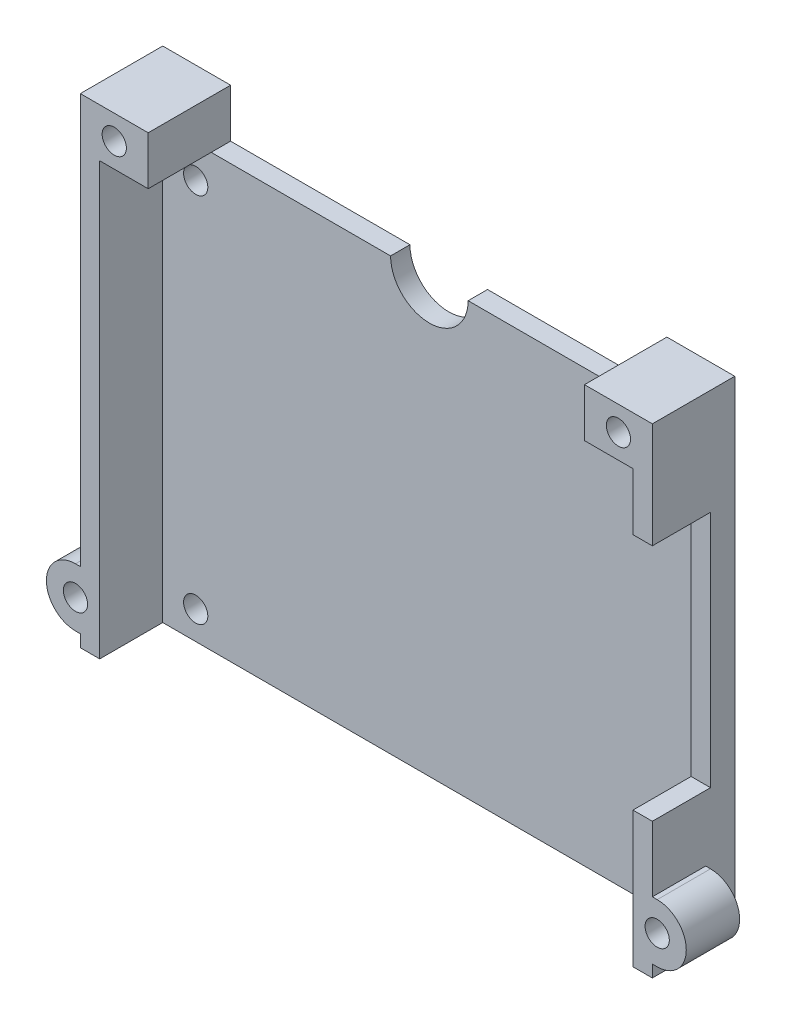
SolidWorks part; units mm, degrees
ref_plane "Front Plane" through (0, 0, 0) normal (0, 0, 1) x (1, 0, 0)
ref_plane "Top Plane" through (0, 0, 0) normal (0, 1, 0) x (1, 0, 0)
ref_plane "Right Plane" through (0, 0, 0) normal (1, 0, 0) x (0, 0, -1)
sketch "Sketch1" plane through (0, 0, 0) normal (0, 1, 0) x (1, 0, 0)
  line L0 (0, 0) -> (2, 0)
  line L1 (0, 0) -> (59, 0) construction
  line L2 (0, 0) -> (0, 8.5)
  line L3 (0, 8.5) -> (59, 8.5)
  line L4 (59, 0) -> (59, 8.5)
  line L5 (2, 0) -> (2, 6.5)
  line L6 (2, 6.5) -> (57, 6.5)
  line L7 (57, 6.5) -> (57, 0)
  line L8 (57, 0) -> (59, 0)
  dimension "D1" = 59
  dimension "D2" = 8.5
  dimension "D3" = 2
  dimension "D4" = 6.5
  dimension "D5" = 55
extrude "Boss-Extrude1" add sketch "Sketch1" along normal blind 44.5
sketch "Sketch2" plane through (59, 0, 0) normal (1, 0, 0) x (0, 0, -1)
  line L0 (0, 0) -> (0, 14) construction
  line L1 (0, 44.5) -> (0, 0) construction
  line L2 (0, 14) -> (6, 14)
  line L3 (6, 14) -> (6, 38.6)
  line L4 (6, 38.6) -> (0, 38.6)
  line L5 (0, 38.6) -> (0, 14)
  dimension "D1" = 14
  dimension "D2" = 6
  dimension "D3" = 24.6
extrude "Cut-Extrude1" cut sketch "Sketch2" against normal blind 10
sketch "Sketch3" plane through (0, 0, -8.5) normal (0, 0, -1) x (-1, 0, 0)
  line L0 (-59, 0) -> (-59, 7.25) construction
  line L1 (-59, 44.5) -> (-59, 0) construction
  line L2 (-59, 7.25) -> (-59, 1.25)
  line L3 (-59, 4.25) -> (-59.5, 4.25) construction
  line L4 (-59, 7.25) -> (-59.5, 7.25)
  line L5 (-59, 1.25) -> (-59.5, 1.25)
  line L6 (0, 0) -> (0, 7.25) construction
  line L7 (0, 44.5) -> (0, 0) construction
  line L8 (0, 7.25) -> (0.5, 7.25)
  line L9 (0, 7.25) -> (0, 1.25)
  line L10 (0, 1.25) -> (0.5, 1.25)
  line L11 (0, 4.25) -> (0.5, 4.25) construction
  arc A0 (-59.5, 7.25) -> (-59.5, 1.25) centre (-59.5, 4.25) ccw
  circle A1 centre (-59.5, 4.25) radius 1.25
  arc A2 (0.5, 7.25) -> (0.5, 1.25) centre (0.5, 4.25) cw
  circle A3 centre (0.5, 4.25) radius 1.25
  line M5 (0, 0) -> (0, 44.5)
  line M7 (-59, 44.5) -> (-59, 0)
  dimension "D4" = 3
  dimension "D5" = 2.5
  dimension "D11" = 3
  dimension "D12" = 2.5
  dimension "D1" = 7.25
  dimension "D2" = 6
  dimension "D3" = 0.5
  dimension "D6" = 7.25
  dimension "D7" = 0.5
  dimension "D8" = 6
  dimension "D9" = 0.5
extrude "Boss-Extrude2" add sketch "Sketch3" against normal blind 8.5 contours A1 L4 A0 L5 M7 | A3 L10 A2 L8 M5 region at (59.0695, 6.3228, -8.5) region at (-0.25, 7.1805, -8.5)
extrude "Cut-Extrude2" cut sketch "Sketch3<3>" against normal blind 11 contours L2 A1 | L9 A3 region at (58.6906, 4.25, -8.5) region at (0.3094, 4.25, -8.5)
sketch "Sketch3<3>" plane through (0, 0, -8.5) normal (0, 0, -1) x (-1, 0, 0) same geometry as "Sketch3"
sketch "Sketch4" plane through (0, 44.5, 0) normal (0, 1, 0) x (1, 0, 0)
  line L0 (59, 8.5) -> (0, 8.5) construction
  line L1 (0, 0) -> (7, 0)
  line L2 (0, 0) -> (0, 8.5)
  line L3 (0, 8.5) -> (7, 8.5)
  line L4 (7, 0) -> (7, 8.5)
  line L6 (59, 0) -> (52, 0)
  line L7 (59, 0) -> (59, 8.5)
  line L8 (59, 8.5) -> (52, 8.5)
  line L9 (52, 0) -> (52, 8.5)
  dimension "D1" = 7
  dimension "D2" = 7
extrude "Boss-Extrude3" add sketch "Sketch4" along normal blind 5
sketch "Sketch5" plane through (0, 0, -8.5) normal (0, 0, -1) x (-1, 0, 0)
  line L0 (-59, 49.5) -> (-52, 44.5) construction
  line L1 (0, 49.5) -> (-7, 44.5) construction
  circle A0 centre (-55.5, 47) radius 1.25
  circle A1 centre (-3.5, 47) radius 1.25
  dimension "D1" = 2.5
  dimension "D2" = 2.5
extrude "Cut-Extrude3" cut sketch "Sketch5" against normal through all
sketch "Sketch7" plane through (0, 0, -8.5) normal (0, 0, -1) x (-1, 0, 0)
  line L0 (-59, 0) -> (-59, 2.9) construction
  line L1 (-59, 1.25) -> (-59, 0) construction
  line L2 (-59, 2.9) -> (0, 2.9) construction
  line L3 (0, 1.25) -> (0, 0) construction
  line L4 (-53.6, 2.9) -> (-5.4, 2.9)
  line L5 (-53.6, 2.9) -> (-53.6, 41.2) construction
  line L6 (-53.6, 41.2) -> (-5.4, 41.2) construction
  circle A0 centre (-53.6, 2.9) radius 1.25
  circle A1 centre (-5.4, 2.9) radius 1.25
  circle A2 centre (-53.6, 41.2) radius 1.25
  circle A3 centre (-5.4, 41.2) radius 1.25
  point P11 (-29.5, 2.9)
  dimension "D3" = 2.5
  dimension "D4" = 2.5
  dimension "D6" = 2.5
  dimension "D8" = 2.5
  dimension "D1" = 2.9
  dimension "D2" = 48.2
  dimension "D5" = 38.3
  dimension "D7" = 48.2
extrude "Cut-Extrude4" cut sketch "Sketch7" against normal blind 10 contours A2 | A3 | A1 | A0 region at (5.4, 4.1146, -8.5) region at (54.8146, 2.9, -8.5) region at (53.6, 41.2, -8.5) region at (5.4, 41.2, -8.5)
sketch "Sketch8" plane through (0, 0, -8.5) normal (0, 0, -1) x (-1, 0, 0)
  line L0 (-52, 44.5) -> (-7, 44.5) construction
  circle A0 centre (-29.5, 44.5) radius 4
  dimension "D1" = 8
extrude "Cut-Extrude5" cut sketch "Sketch8" against normal through all
extrude "Cut-Extrude6" cut sketch "Sketch3<4>" against normal blind 3 contours A1 L4 A0 L5 M7 | A3 L10 A2 L8 M5 region at (59.0695, 6.3228, -8.5) region at (-0.25, 7.1805, -8.5)
sketch "Sketch3<4>" plane through (0, 0, -8.5) normal (0, 0, -1) x (-1, 0, 0) same geometry as "Sketch3"
extrude "Boss-Extrude4" add sketch "Sketch3<5>" against normal blind 3 contours L9 A3 | L2 A1 region at (58.6906, 4.25, -8.5) region at (0.3094, 4.25, -8.5)
sketch "Sketch3<5>" plane through (0, 0, -8.5) normal (0, 0, -1) x (-1, 0, 0) same geometry as "Sketch3"
